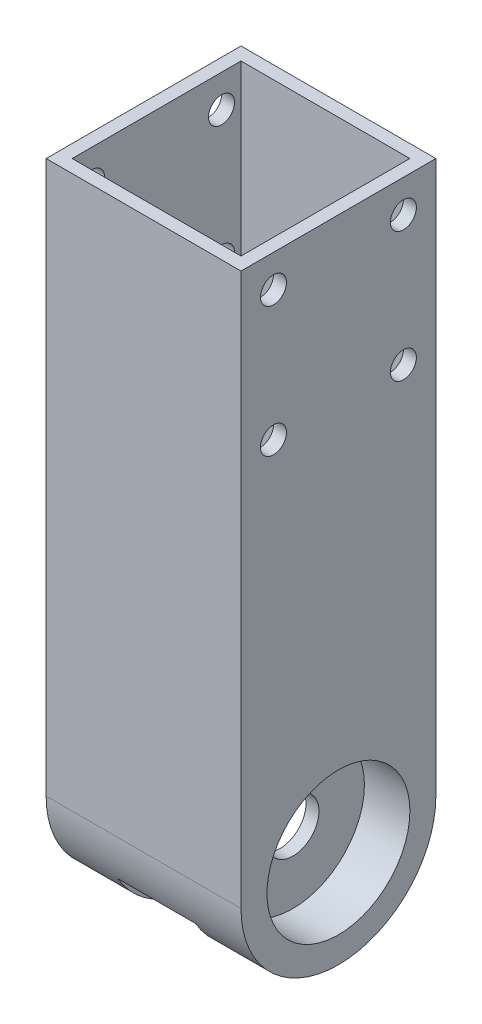
SolidWorks part; units mm, degrees
ref_plane "Front Plane" through (0, 0, 0) normal (0, 0, 1) x (1, 0, 0)
ref_plane "Top Plane" through (0, 0, 0) normal (0, 1, 0) x (1, 0, 0)
ref_plane "Right Plane" through (0, 0, 0) normal (1, 0, 0) x (0, 0, -1)
sketch "Sketch1" plane through (0, 0, 0) normal (0, 1, 0) x (1, 0, 0)
  line L1 (-15, -15) -> (15, -15)
  line L2 (-15, -15) -> (-15, 15)
  line L3 (-15, 15) -> (15, 15)
  line L4 (15, -15) -> (15, 15)
  line L5 (-15, -15) -> (15, 15) construction
  line L6 (-15, 15) -> (15, -15) construction
  line L11 (-6, -6) -> (6, 6) construction
  line L12 (-6, 6) -> (6, -6) construction
  line L13 (-6, -13) -> (6, -13)
  line L14 (-6, -13) -> (-6, 13)
  line L15 (-6, 13) -> (6, 13)
  line L16 (6, -13) -> (6, 13)
  line L17 (-6, -13) -> (6, 13) construction
  line L18 (-6, 13) -> (6, -13) construction
  point P0 (0, 0)
  point P6 (0, 0)
  point P11 (0, 0)
  dimension "D1" = 30
  dimension "D2" = 30
  dimension "D3" = 9
  dimension "D4" = 2
extrude "Boss-Extrude2" add sketch "Sketch1" along normal blind 100
sketch "Sketch2" plane through (15, 0, 0) normal (1, 0, 0) x (0, 0, -1)
  line L0 (-15, 95) -> (15, 95)
  line L1 (-15, 100) -> (-15, 0) construction
  line L2 (15, 100) -> (15, 0) construction
  line L3 (-15, 100) -> (15, 100) construction
  line L4 (-15, 100) -> (-15, 70) construction
  line L5 (-15, 70) -> (15, 70) construction
  line L6 (-15, 70) -> (15, 70)
  circle A0 centre (-10, 95) radius 2
  circle A1 centre (10, 95) radius 2
  circle A4 centre (-10, 75) radius 2
  circle A5 centre (10, 75) radius 2
  point P16 (0, 0)
  point P24 (19.9846, 65.2254)
  dimension "D2" = 4
  dimension "D4" = 4
  dimension "D7" = 5
  dimension "D9" = 5
  dimension "D11" = 4
  dimension "D13" = 4
  dimension "D1" = 5
  dimension "D3" = 5
  dimension "D5" = 5
  dimension "D6" = 30
  dimension "D10" = 5
  dimension "D12" = 5
extrude "Cut-Extrude1" cut sketch "Sketch2" against normal blind 51 contours A1 | A5 | A0 | A4
sketch "Sketch3" plane through (0, 100, 0) normal (0, 1, 0) x (1, 0, 0)
  line L0 (-6, 13) -> (-13, 13)
  line L1 (-15, 15) -> (-15, -15) construction
  line L2 (-13, 13) -> (-13, -13)
  line L7 (-6, -13) -> (-13, -13)
  line L8 (-6, 13) -> (-6, -13)
  line L10 (6, 13) -> (13, 13)
  line L11 (6, 13) -> (6, -13)
  line L12 (6, -13) -> (13, -13)
  line L13 (13, 13) -> (13, -13)
  dimension "D1" = 2
  dimension "D2" = 2
extrude "Cut-Extrude2" cut sketch "Sketch3" against normal blind 70
fillet "Fillet1" radius 15 2 edges at (0, 0, -15) (0, 0, 15)
sketch "Sketch5" plane through (15, 0, 0) normal (1, 0, 0) x (0, 0, -1)
  circle A0 centre (0, 15) radius 4
  dimension "D1" = 8
extrude "Cut-Extrude3" cut sketch "Sketch5" against normal blind 50
sketch "Sketch6" plane through (15, 0, 0) normal (1, 0, 0) x (0, 0, -1)
  circle A0 centre (0, 15) radius 11
  dimension "D1" = 22
extrude "Cut-Extrude4" cut sketch "Sketch6" against normal blind 7
sketch "Sketch7" plane through (-15, 0, 0) normal (-1, 0, 0) x (0, 0, 1)
  circle A0 centre (0, 15) radius 11
  dimension "D1" = 22
extrude "Cut-Extrude5" cut sketch "Sketch7" against normal blind 7
